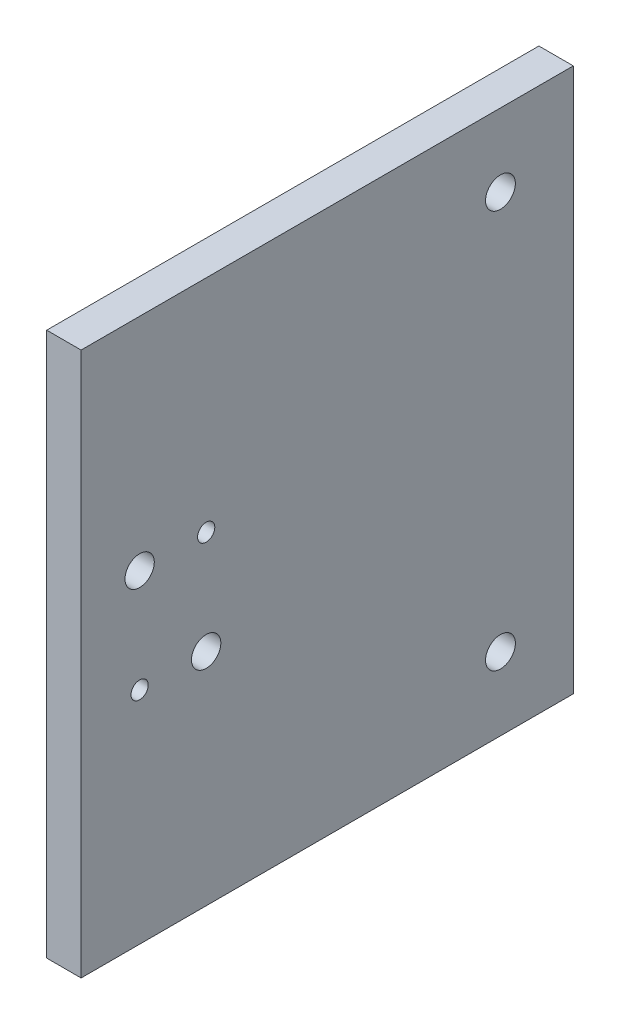
SolidWorks part; units mm, degrees
ref_plane "Front Plane" through (0, 0, 0) normal (1, 0, 0) x (0, 1, 0)
ref_plane "Top Plane" through (0, 0, 0) normal (0, 0, 1) x (0, 1, 0)
ref_plane "Right Plane" through (0, 0, 0) normal (0, 1, 0) x (-1, 0, 0)
sketch "Sketch1" plane through (0, 0, 0) normal (1, 0, 0) x (0, 1, 0)
  line L0 (0, 25) -> (0, -25) construction
  line L1 (-47.4, -25) -> (47.4, -25) construction
  line L2 (-47.4, -25) -> (-47.4, 25) construction
  line L3 (-47.4, 25) -> (47.4, 25) construction
  line L4 (47.4, -25) -> (47.4, 25) construction
  line L5 (-47.4, -25) -> (47.4, 25) construction
  line L6 (-47.4, 25) -> (47.4, -25) construction
  line L8 (-9, -5.8) -> (9, -5.8) construction
  line L9 (-9, -5.8) -> (-9, 5.8) construction
  line L10 (-9, 5.8) -> (9, 5.8) construction
  line L11 (9, -5.8) -> (9, 5.8) construction
  line L12 (-9, -5.8) -> (9, 5.8) construction
  line L13 (-9, 5.8) -> (9, -5.8) construction
  line L14 (-34.7, -15) -> (34.7, -15) construction
  line L15 (-34.7, -15) -> (-34.7, 15) construction
  line L16 (-34.7, 15) -> (34.7, 15) construction
  line L17 (34.7, -15) -> (34.7, 15) construction
  line L18 (-34.7, -15) -> (34.7, 15) construction
  line L19 (-34.7, 15) -> (34.7, -15) construction
  line L20 (-47.4, -25) -> (47.4, -25) construction
  line L21 (-47.4, -25) -> (-47.4, -69.8)
  line L22 (-47.4, -69.8) -> (47.4, -69.8)
  line L23 (47.4, -25) -> (47.4, -69.8) construction
  line L24 (-47.4, -69.8) -> (-34.7, -69.8) construction
  line L25 (-47.4, -69.8) -> (-47.4, -57.1) construction
  line L26 (-47.4, -57.1) -> (-34.7, -57.1) construction
  line L27 (-34.7, -69.8) -> (-34.7, -57.1) construction
  line L28 (47.4, -69.8) -> (34.7, -69.8) construction
  line L29 (47.4, -69.8) -> (47.4, -57.1) construction
  line L30 (47.4, -57.1) -> (34.7, -57.1) construction
  line L31 (34.7, -69.8) -> (34.7, -57.1) construction
  line L34 (47.4, -69.8) -> (47.4, 16)
  line L40 (-47.4, -25) -> (-47.4, 16)
  line L43 (-47.4, 16) -> (47.4, 16)
  line L44 (-47.4, -44.4) -> (47.4, -44.4) construction
  circle A0 centre (-9, 5.8) radius 1.5
  circle A1 centre (-9, -5.8) radius 2.555
  circle A2 centre (9, -5.8) radius 1.5
  circle A3 centre (9, 5.8) radius 2.555
  circle A4 centre (-34.7, 15) radius 2.555 construction
  circle A5 centre (-34.7, -15) radius 2.555 construction
  circle A6 centre (34.7, 15) radius 2.555 construction
  circle A7 centre (34.7, -15) radius 2.555 construction
  circle A8 centre (-34.7, -57.1) radius 2.6
  circle A9 centre (34.7, -57.1) radius 2.6
  point P0 (0, 0)
  point P8 (0, 0)
  point P17 (0, 0)
  point P36 (47.4, 20.7959)
  point P39 (47.4, 29.7184)
  point P42 (-47.4, 17.3549)
  point P44 (0, 0)
  point P45 (-47.4, 18.3547)
  point P46 (-47.2242, -24.9073)
  point P47 (47.4, 52.7117)
  dimension "D5" = 5.11
  dimension "D6" = 3
  dimension "D9" = 5.11
  dimension "D10" = 5.11
  dimension "D11" = 5.11
  dimension "D12" = 3
  dimension "D13" = 3
  dimension "D17" = 5.2
  dimension "D20" = 10.2
  dimension "D1" = 11.6
  dimension "D2" = 18
  dimension "D3" = 94.8
  dimension "D4" = 50
  dimension "D7" = 12.7
  dimension "D8" = 30
  dimension "D14" = 38.6
  dimension "D15" = 12.7
  dimension "D16" = 12.7
  dimension "D19" = 25.4
extrude "Boss-Extrude1" add sketch "Sketch1" along normal blind 6
